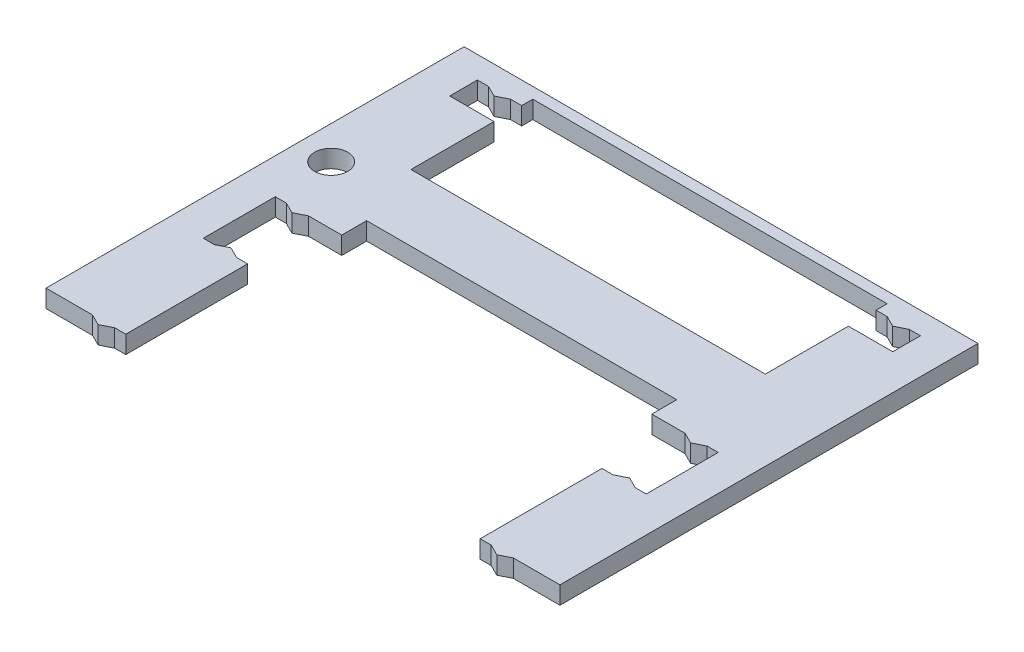
SolidWorks part; units mm, degrees
ref_plane "Front Plane" through (0, 0, 0) normal (0, 0, 1) x (1, 0, 0)
ref_plane "Top Plane" through (0, 0, 0) normal (0, 1, 0) x (1, 0, 0)
ref_plane "Right Plane" through (0, 0, 0) normal (1, 0, 0) x (0, 0, -1)
sketch "Sketch1" plane through (0, 0, 0) normal (0, 1, 0) x (1, 0, 0)
  line L0 (-65.8326, 0) -> (-61.6296, 0)
  line L1 (-58.6296, 0) -> (-58.6296, 11)
  line L2 (-58.6296, 11) -> (-59.6296, 11)
  line L3 (-62.6296, 11) -> (-62.6296, 17.5)
  line L4 (-62.6296, 17.5) -> (-61.6296, 17.5)
  line L5 (-61.6296, 17.5) -> (-60.6296, 17)
  line L6 (-60.6296, 38.9626) -> (-60.6296, -4.5955) construction
  line L7 (-56.6296, 17.5) -> (-56.6296, 19.75)
  line L8 (-26.6296, 25.75) -> (-58.6296, 25.75)
  line L9 (-58.6296, 25.75) -> (-58.6296, 33.25)
  line L10 (-58.6296, 35.75) -> (-58.6296, 36.75)
  line L11 (-42.6296, 37.75) -> (-42.6296, 3.1352) construction
  line L12 (-65.8326, 0) -> (-65.8326, 37.75)
  line L13 (-65.8326, 37.75) -> (-19.4266, 37.75)
  line L14 (-24.6296, 38.9626) -> (-24.6296, -4.5955) construction
  line L15 (-25.6296, 35.75) -> (-26.6296, 35.75)
  line L16 (-24.6296, 35.25) -> (-25.6296, 35.75)
  line L17 (-23.6296, 35.75) -> (-24.6296, 35.25)
  line L18 (-22.6296, 35.75) -> (-23.6296, 35.75)
  line L19 (-58.6296, 33.25) -> (-62.6296, 33.25)
  line L20 (-22.6296, 33.25) -> (-22.6296, 35.75)
  line L21 (-25.6296, 17.5) -> (-28.6296, 17.5)
  line L22 (-24.6296, 17) -> (-25.6296, 17.5)
  line L23 (-25.6296, 0) -> (-26.6296, 0)
  line L24 (-24.6296, -0.5) -> (-25.6296, 0)
  line L25 (-23.6296, 0) -> (-24.6296, -0.5)
  line L26 (-24.6296, 11.5) -> (-25.6296, 11)
  line L27 (-62.6296, 11) -> (-61.6296, 11)
  line L28 (-61.6296, 11) -> (-60.6296, 11.5)
  line L29 (-60.6296, 11.5) -> (-59.6296, 11)
  line L30 (-61.6296, 0) -> (-60.6296, -0.5)
  line L31 (-60.6296, -0.5) -> (-59.6296, 0)
  line L32 (-59.6296, 0) -> (-58.6296, 0)
  line L33 (-60.6296, 17) -> (-59.6296, 17.5)
  line L34 (-59.6296, 17.5) -> (-56.6296, 17.5)
  line L35 (-56.6296, 19.75) -> (-28.6296, 19.75)
  line L36 (-62.6296, 33.25) -> (-62.6296, 35.75)
  line L37 (-62.6296, 35.75) -> (-61.6296, 35.75)
  line L38 (-58.6296, 36.75) -> (-26.6296, 36.75)
  line L39 (-61.6296, 35.75) -> (-60.6296, 35.25)
  line L40 (-60.6296, 35.25) -> (-59.6296, 35.75)
  line L41 (-59.6296, 35.75) -> (-58.6296, 35.75)
  line L42 (-23.6296, 11) -> (-24.6296, 11.5)
  line L43 (-22.6296, 11) -> (-23.6296, 11)
  line L44 (-26.6296, 33.25) -> (-22.6296, 33.25)
  line L45 (-19.4266, 0) -> (-19.4266, 37.75)
  line L46 (-26.6296, 35.75) -> (-26.6296, 36.75)
  line L47 (-26.6296, 25.75) -> (-26.6296, 33.25)
  line L48 (-28.6296, 17.5) -> (-28.6296, 19.75)
  line L49 (-23.6296, 17.5) -> (-24.6296, 17)
  line L50 (-22.6296, 17.5) -> (-23.6296, 17.5)
  line L51 (-22.6296, 11) -> (-22.6296, 17.5)
  line L52 (-26.6296, 11) -> (-25.6296, 11)
  line L53 (-26.6296, 0) -> (-26.6296, 11)
  line L54 (-19.4266, 0) -> (-23.6296, 0)
  circle A0 centre (-62.8326, 22.75) radius 1.5
  point P19 (-42.6296, 34.75)
  point P20 (-42.6296, 37.75)
  point P26 (-42.6296, 36.75)
  point P29 (-42.6296, 19.75)
  point P62 (-42.6296, 25.75)
  dimension "D26" = 3
  dimension "D27" = 3
  dimension "D1" = 23.203
  dimension "D2" = 16
  dimension "D3" = 1
  dimension "D4" = 1
  dimension "D5" = 1
  dimension "D6" = 2
  dimension "D7" = 0.5
  dimension "D8" = 6.5
  dimension "D9" = 0.5
  dimension "D10" = 1
  dimension "D11" = 1
  dimension "D12" = 11
  dimension "D13" = 0.5
  dimension "D14" = 1
  dimension "D15" = 1
  dimension "D16" = 2.25
  dimension "D17" = 3
  dimension "D18" = 6
  dimension "D19" = 1
  dimension "D20" = 7.5
  dimension "D21" = 16
  dimension "D22" = 20
  dimension "D23" = 1
  dimension "D24" = 1
  dimension "D25" = 0.5
  dimension "D28" = 2.5
extrude "Boss-Extrude1" add sketch "Sketch1" along normal blind 1.6
